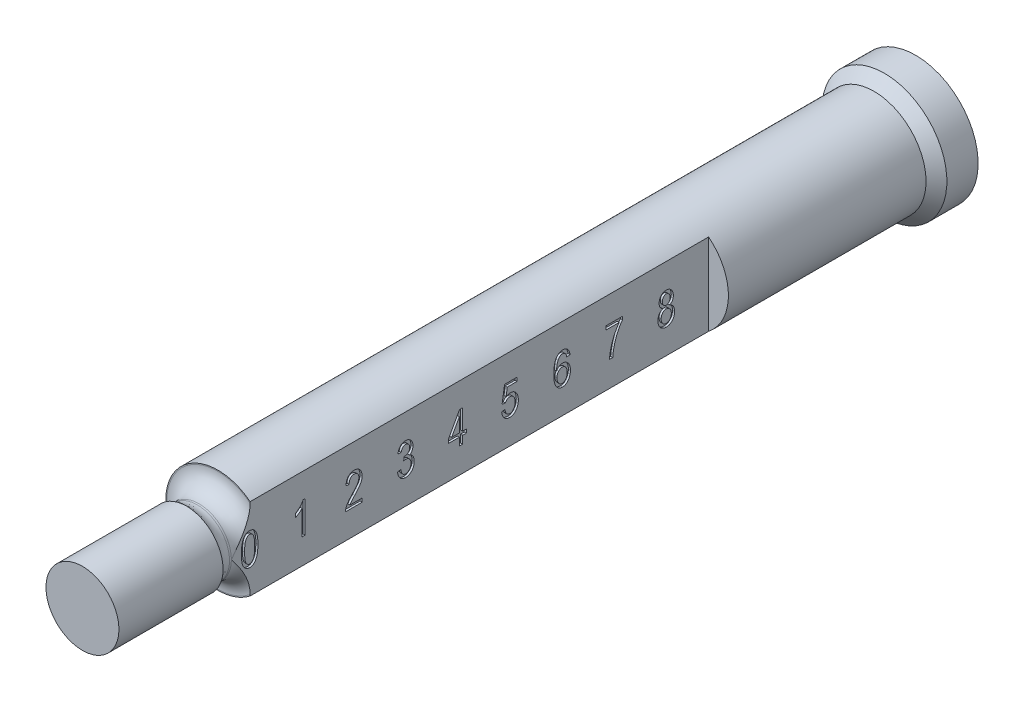
SolidWorks part; units mm, degrees
material "AISI 1020"
ref_plane "Plano superior" through (0, 0, 0) normal (0, 0, 1) x (1, 0, 0)
ref_plane "Plano frontal" through (0, 0, 0) normal (0, 1, 0) x (1, 0, 0)
ref_plane "Plano direito" through (0, 0, 0) normal (1, 0, 0) x (0, 0, -1)
sketch "Esboço1" plane through (0, 0, 0) normal (0, 1, 0) x (1, 0, 0)
  line L0 (0, 0) -> (3.5, 0)
  line L1 (3.5, 0) -> (3.5, 10)
  line L2 (3.5, 10) -> (3.1, 10)
  line L3 (3.1, 10) -> (3.1, 11.2)
  line L4 (4.9, 13) -> (5, 13)
  line L5 (5, 13) -> (5, 76)
  line L6 (5, 76) -> (6, 76)
  line L7 (6, 76) -> (6, 80)
  line L8 (6, 80) -> (0, 80)
  line L9 (0, 80) -> (0, 0)
  arc A0 (4.9, 13) -> (3.1, 11.2) centre (4.9, 11.2) ccw
  point P13 (3.1, 13)
  dimension "D9" = 1.8
  dimension "D1" = 4
  dimension "D2" = 3
  dimension "D3" = 10
  dimension "D4" = 80
  dimension "D5" = 5
  dimension "D6" = 6
  dimension "D7" = 3.5
  dimension "D8" = 3.1
revolve "Revolução1" add sketch "Esboço1" angle 360 about L9
cosmetic thread "Representação de rosca3" parameters "D2"=8.344
fillet "Filete1" radius 1.5 1 edges at (-3.1, 0, -10)
chamfer "Chanfro3" distance 1 angle 45 1 edges at (-6, 0, -76)
sketch "Esboço18" plane through (0, 0, 0) normal (0, 1, 0) x (1, 0, 0)
  line L4 (3.1, 11.2) -> (9.2217, 11.2)
  line L5 (3.1, 11.2) -> (3.1, 57.0221)
  line L6 (3.1, 57.0221) -> (9.2217, 57.0221)
  line L7 (9.2217, 11.2) -> (9.2217, 57.0221)
extrude "Corte-extrusão1" cut sketch "Esboço18" against normal mid plane 10
sketch "Esboço21" plane through (3.1, 0, 0) normal (1, 0, 0) x (0, 0, -1)
  line L0 (17, -1.5021) -> (22, -1.5021) construction
  line L3 (22, -1.5021) -> (27, -1.5021) construction
  line L4 (18, 7.2255) -> (18, 0) construction
  line L5 (13, -1.5021) -> (17, -1.5021) construction
  line L6 (23, 9.0452) -> (23, 1.209) construction
  line L7 (27, -1.5021) -> (32, -1.5021) construction
  line L8 (37, -1.5021) -> (32, -1.5021) construction
  line L9 (37, -1.5021) -> (42, -1.5021) construction
  line L10 (42, -1.5021) -> (47, -1.5021) construction
  line L11 (47, -1.5021) -> (52, -1.5021) construction
  line L12 (52, -1.5021) -> (57, -1.5021) construction
  line L13 (13, -1.5021) -> (12, -1.5021) construction
  text T0 "1" font "Arial Narrow" height 3
  text T1 "2" font "Arial Narrow" height 3
  text T2 "3" font "Arial Narrow" height 3
  text T3 "4" font "Arial Narrow" height 3
  text T4 "5" font "Arial Narrow" height 3
  text T5 "6" font "Arial Narrow" height 3
  text T6 "7" font "Arial Narrow" height 3
  text T7 "8" font "Arial Narrow" height 3
  text T8 "0" font "Arial Narrow" height 3
  point P15 (12, -1.6258)
  dimension "D1" = 4
  dimension "D2" = 5
  dimension "D3" = 5
  dimension "D4" = 5
  dimension "D5" = 5
  dimension "D6" = 5
  dimension "D7" = 5
  dimension "D8" = 5
  dimension "D9" = 5
  dimension "D10" = 5
  dimension "D11" = 5
  dimension "D12" = 1
extrude "Corte-extrusão3" cut sketch "Esboço21" against normal blind 0.2
